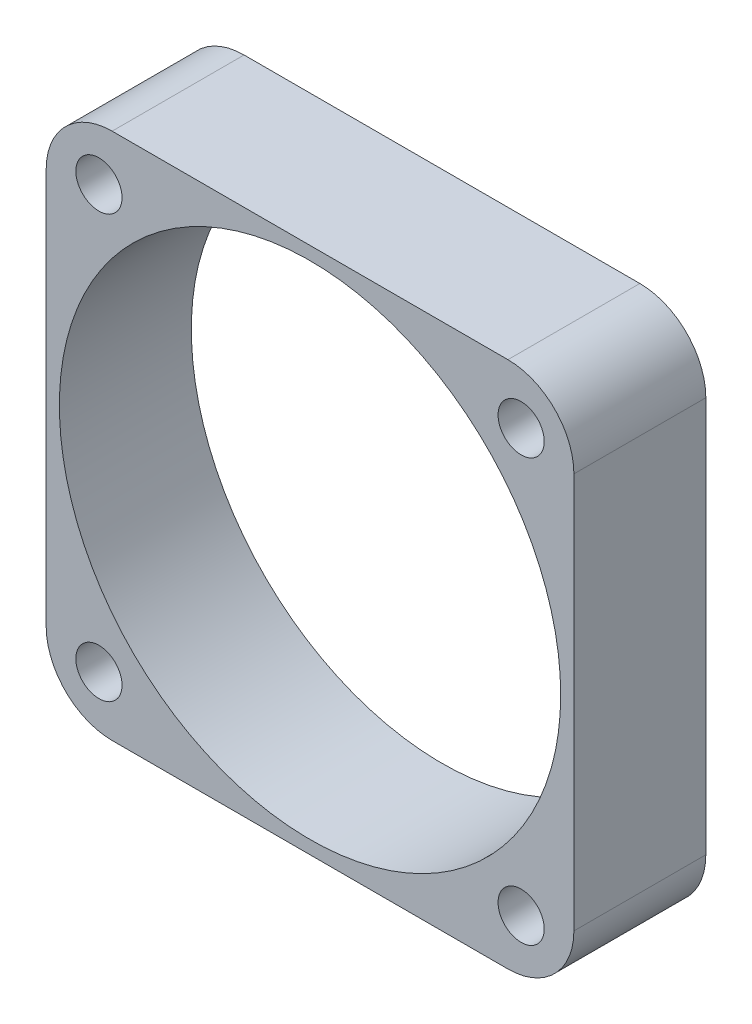
SolidWorks part; units mm, degrees
material "ABS PC"
ref_plane "Front Plane" through (0, 0, 0) normal (0, 0, 1) x (1, 0, 0)
ref_plane "Top Plane" through (0, 0, 0) normal (0, 1, 0) x (1, 0, 0)
ref_plane "Right Plane" through (0, 0, 0) normal (1, 0, 0) x (0, 0, -1)
sketch "Sketch1" plane through (0, 0, 0) normal (0, 0, 1) x (1, 0, 0)
  line L1 (0, 0) -> (40, 0)
  line L2 (0, 0) -> (0, 40)
  line L3 (0, 40) -> (40, 40)
  line L4 (40, 0) -> (40, 40)
  dimension "D1" = 40
  dimension "D2" = 40
extrude "Boss-Extrude1" add sketch "Sketch1" along normal blind 10
sketch "Sketch3" plane through (0, 0, 10) normal (0, 0, 1) x (1, 0, 0)
  line L0 (0, 20) -> (20, 20) construction
  line L1 (0, 40) -> (0, 0) construction
  line L2 (20, 20) -> (20, 0) construction
  line L3 (0, 0) -> (40, 0) construction
  circle A0 centre (20, 20) radius 19
  circle A1 centre (4, 36) radius 1.75
  circle A2 centre (36, 36) radius 1.75
  circle A3 centre (36, 4) radius 1.75
  circle A4 centre (4, 4) radius 1.75
  dimension "D1" = 38
  dimension "D6" = 3.5
  dimension "D2" = 32
  dimension "D3" = 32
  dimension "D4" = 32
  dimension "D5" = 32
extrude "Cut-Extrude1" cut sketch "Sketch3" against normal blind 10 contours A0 | A1 | A4 | A3 | A2 region at (20, 20, 10) region at (4, 36, 10) region at (36, 36, 10) region at (36, 4, 10) region at (4, 4, 10)
fillet "Fillet1" radius 5 4 edges at (0, 0, 5) (40, 0, 5) (0, 40, 5) (40, 40, 5)
